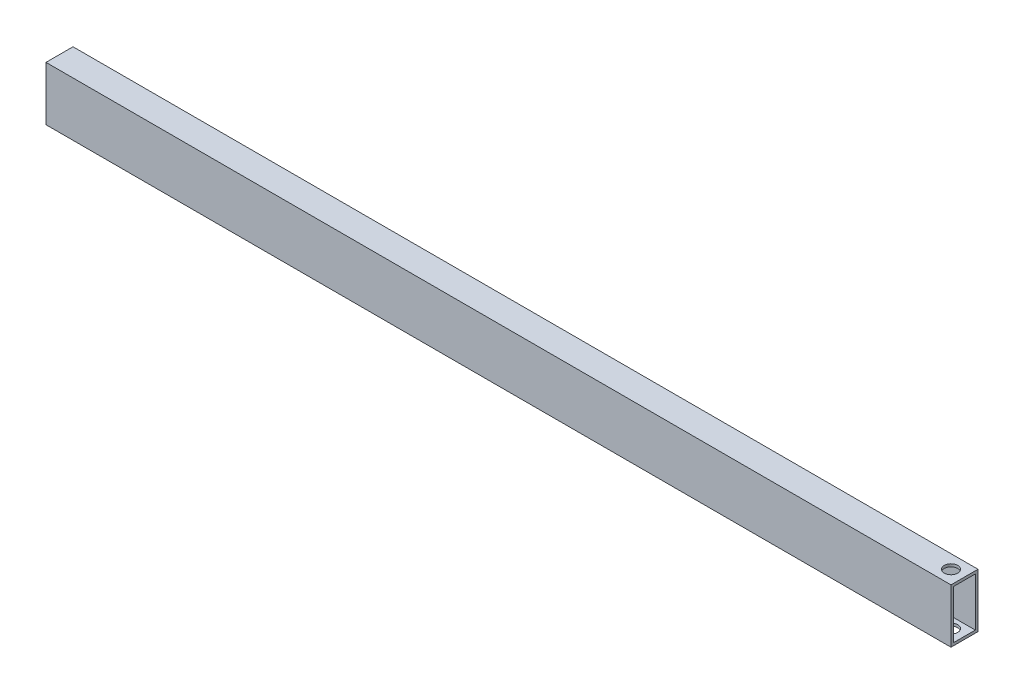
SolidWorks part; units mm, degrees
ref_plane "Front Plane" through (0, 0, 0) normal (0, 0, 1) x (1, 0, 0)
ref_plane "Top Plane" through (0, 0, 0) normal (0, 1, 0) x (1, 0, 0)
ref_plane "Right Plane" through (0, 0, 0) normal (1, 0, 0) x (0, 0, -1)
sketch "Sketch1" plane through (0, 0, 0) normal (1, 0, 0) x (0, 0, -1)
  line L0 (4, -5.0106) -> (4, 12.9894)
  line L1 (5, -6.0106) -> (-5, -6.0106)
  line L2 (5, -6.0106) -> (5, 13.9894)
  line L3 (5, 13.9894) -> (-5, 13.9894)
  line L4 (-5, -6.0106) -> (-5, 13.9894)
  line L5 (5, -6.0106) -> (-5, 13.9894) construction
  line L6 (5, 13.9894) -> (-5, -6.0106) construction
  line L7 (4, 12.9894) -> (-4, 12.9894)
  line L8 (-4, -5.0106) -> (-4, 12.9894)
  line L9 (4, -5.0106) -> (-4, -5.0106)
  point P0 (0, 3.9894)
  dimension "D1" = 10
  dimension "D2" = 20
  dimension "D3" = 1
extrude "Boss-Extrude1" add sketch "Sketch1" along normal blind 225 and the other way blind 110
sketch "Sketch3" plane through (0, 0, -5) normal (0, 0, -1) x (-1, 0, 0)
  line L0 (0, -6.0106) -> (0, 13.9894) construction
  line L1 (110, -6.0106) -> (-225, -6.0106) construction
  line L2 (110, 13.9894) -> (-225, 13.9894) construction
  circle A0 centre (-19.85, 3.9894) radius 2.5
  circle A1 centre (-10, 3.9894) radius 2.5
  circle A2 centre (0, 3.9894) radius 2.5
  circle A3 centre (10, 3.9894) radius 2.5
  circle A4 centre (19.85, 3.9894) radius 2.5
  dimension "D5" = 5
  dimension "D6" = 5
  dimension "D7" = 5
  dimension "D1" = 9.85
  dimension "D2" = 10
  dimension "D3" = 10
  dimension "D8" = 9.85
  dimension "D9" = 10
extrude "Cut-Extrude1" cut sketch "Sketch3" against normal blind 1
sketch "Sketch4" plane through (0, 13.9894, 0) normal (0, 1, 0) x (1, 0, 0)
  line L0 (-110, 5) -> (-110, -5) construction
  line L1 (-110, 5) -> (225, 5) construction
  line L2 (225, 5) -> (225, -5) construction
  circle A0 centre (-105, 0) radius 2.5 construction
  circle A1 centre (220, 0) radius 2.5
  dimension "D1" = 5
  dimension "D4" = 5
  dimension "D2" = 5
  dimension "D3" = 5
  dimension "D5" = 5
  dimension "D6" = 5
extrude "Cut-Extrude2" cut sketch "Sketch4" against normal blind 20
